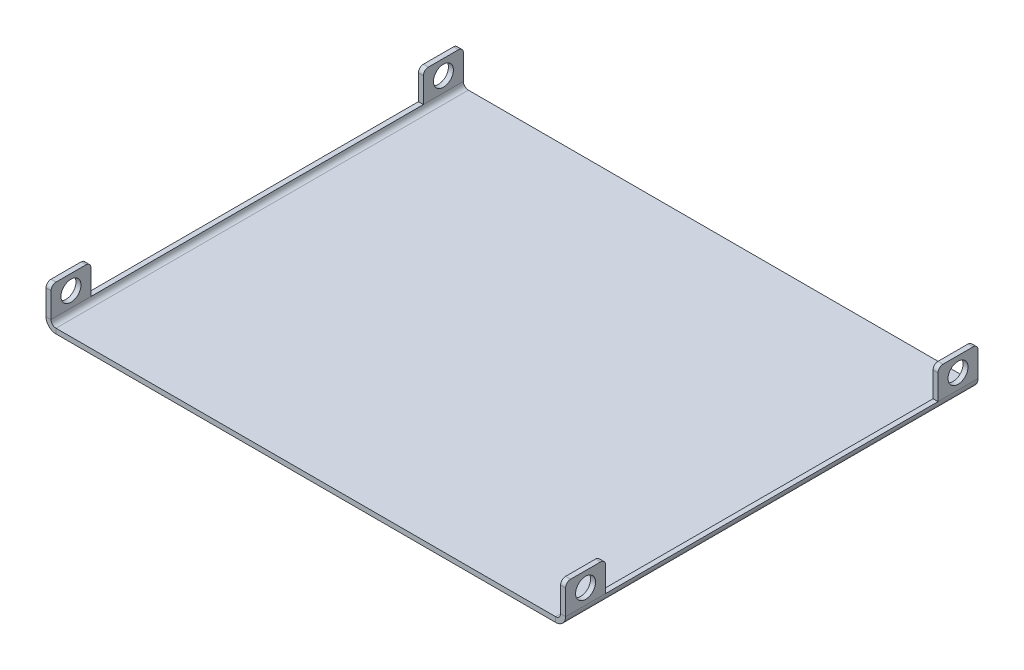
SolidWorks part; units mm, degrees
note: The reader was unsure of these and kept them because the rebuilt part matched: flange length of "Edge-Flange1".
material "6061-T6 (SS)"
ref_plane "Front Plane" through (0, 0, 0) normal (0, 0, 1) x (1, 0, 0)
ref_plane "Top Plane" through (0, 0, 0) normal (0, 1, 0) x (1, 0, 0)
ref_plane "Right Plane" through (0, 0, 0) normal (1, 0, 0) x (0, 0, -1)
sketch "Sketch1" plane through (0, 0, 0) normal (0, 1, 0) x (1, 0, 0)
  line L2 (0, 0) -> (0, 82.6)
  line L4 (104.072, 0) -> (104.072, 82.6)
  line L31 (0, 82.6) -> (104.072, 82.6)
  line L32 (0, 0) -> (104.072, 0)
  dimension "D1" = 82.6
  dimension "D2" = 104.072
  dimension "D3" = 90
base flange "Base-Flange2" sketch "Sketch1" thickness 1 reverse thickness direction no parameters "D1"=1
edge flange "Edge-Flange1" sketch "Sketch14" flange profiles "Sketch14", "Sketch15" flange angle 90 flange length 8 flange position material inside bend radius 1 thickness 1 relief rectangular parameters "D6"=10, "D8"=1
sketch "Sketch14" plane through (104.072, 0, 0) normal (1, 0, 0) x (0, 0, -1)
  line L0 (0, 0) -> (82.6, 0) construction
  line L1 (0, 0) -> (82.6, 0)
  line L2 (0, 0) -> (0, 7)
  line L3 (0, 7) -> (82.6, 7)
  line L4 (82.6, 7) -> (82.6, 0)
  dimension "D1" = 7
sketch "Sketch15" plane through (0, 0, 0) normal (-1, 0, 0) x (0, 0, 1)
  line L0 (-82.6, 0) -> (0, 0) construction
  line L1 (-82.6, 0) -> (0, 0)
  line L2 (-82.6, 0) -> (-82.6, 7)
  line L3 (-82.6, 7) -> (0, 7)
  line L4 (0, 7) -> (0, 0)
  dimension "D1" = 7
bend "EdgeBend1" bend radius 1 bend angle 90 parameters "D5"=1
bend "EdgeBend2" bend radius 1 bend angle 90 parameters "D5"=2
sketch "Sketch16" plane through (104.072, 0, 0) normal (1, 0, 0) x (0, 0, -1)
  line L0 (82.6, 1) -> (0, 1) construction
  line L1 (8, 8) -> (74.6, 8)
  line L2 (8, 8) -> (8, 1)
  line L3 (8, 1) -> (74.6, 1)
  line L4 (74.6, 8) -> (74.6, 1)
  line L5 (0, 7) -> (0, 1) construction
  line L6 (82.6, 1) -> (82.6, 7) construction
  line L7 (82.6, 7) -> (0, 7) construction
  dimension "D1" = 8
  dimension "D2" = 8
  dimension "D3" = 1
extrude "Cut-Extrude1" cut sketch "Sketch16" against normal through all normal cut yes
fillet "Fillet1" radius 1 8 edges at (0.5, 7, -8) (0.5, 7, 0) (0.5, 7, -74.6) (0.5, 7, -82.6) (103.572, 7, -74.6) (103.572, 7, -82.6) (103.572, 7, 0) (103.572, 7, -8)
sketch "Sketch17" plane through (104.072, 0, 0) normal (1, 0, 0) x (0, 0, -1)
  line L0 (8, 1) -> (0, 1) construction
  line L1 (0, 6) -> (0, 1) construction
  line L2 (82.6, 1) -> (74.6, 1) construction
  line L3 (82.6, 1) -> (82.6, 6) construction
  circle A0 centre (4, 4) radius 2
  circle A1 centre (78.6, 4) radius 2
  dimension "D1" = 4
  dimension "D4" = 4
  dimension "D2" = 3
  dimension "D3" = 4
  dimension "D5" = 3
  dimension "D6" = 4
extrude "Cut-Extrude2" cut sketch "Sketch17" against normal through all normal cut yes
sketch "Bend-Lines3" [suppressed] plane through (0, 0, 0) normal (0, 1, 0) x (1, 0, 0)
sketch "Bounding-Box3" [suppressed] plane through (0, 0, 0) normal (0, 1, 0) x (1, 0, 0)
sheet metal parameters "Sheet-Metal2" thickness 1 parameters "D1"=1
flat pattern "Flat-Pattern2" [suppressed]
sketch "Bend-Lines4" plane through (0, 0, 0) normal (0, 1, 0) x (1, 0, 0)
sketch3d "Bounding-Box4" [suppressed]
  line L0 (-135.6338, 86.2583, 0) -> (0, 86.2583, 0) construction
  line L1 (-135.6338, 0, 0) -> (0, 0, 0) construction
  line L2 (-135.6338, 86.2583, 0) -> (-135.6338, 0, 0) construction
  line L3 (0, 86.2583, 0) -> (0, 0, 0) construction
sheet metal parameters "Sheet-Metal3" thickness 1 parameters "D1"=1
flat pattern "Flat-Pattern2"
sketch "Bend-Lines4" plane through (0, 0, 0) normal (0, 1, 0) x (1, 0, 0)
sketch3d "Bounding-Box4" [suppressed]
  line L0 (-135.6338, 86.2583, 0) -> (0, 86.2583, 0) construction
  line L1 (-135.6338, 0, 0) -> (0, 0, 0) construction
  line L2 (-135.6338, 86.2583, 0) -> (-135.6338, 0, 0) construction
  line L3 (0, 86.2583, 0) -> (0, 0, 0) construction
bend of the flat pattern "Flatten-<EdgeBend1>1"
bend of the flat pattern "Flatten-<EdgeBend2>1"
sheet metal parameters "Sheet-Metal4" thickness 1 parameters "D1"=1
flat pattern "Flat-Pattern2"
sketch "Bend-Lines4" plane through (0, 0, 0) normal (0, 1, 0) x (1, 0, 0)
sketch3d "Bounding-Box4" [suppressed]
  line L0 (-135.6338, 86.2583, 0) -> (0, 86.2583, 0) construction
  line L1 (-135.6338, 0, 0) -> (0, 0, 0) construction
  line L2 (-135.6338, 86.2583, 0) -> (-135.6338, 0, 0) construction
  line L3 (0, 86.2583, 0) -> (0, 0, 0) construction
bend of the flat pattern "Flatten-<EdgeBend1>1"
bend of the flat pattern "Flatten-<EdgeBend2>1"
sheet metal parameters "Sheet-Metal5" thickness 1 parameters "D1"=1
flat pattern "Flat-Pattern2"
sketch "Bend-Lines4" plane through (0, 0, 0) normal (0, 1, 0) x (1, 0, 0)
sketch3d "Bounding-Box4" [suppressed]
  line L0 (-135.6338, 86.2583, 0) -> (0, 86.2583, 0) construction
  line L1 (-135.6338, 0, 0) -> (0, 0, 0) construction
  line L2 (-135.6338, 86.2583, 0) -> (-135.6338, 0, 0) construction
  line L3 (0, 86.2583, 0) -> (0, 0, 0) construction
bend of the flat pattern "Flatten-<EdgeBend1>1"
bend of the flat pattern "Flatten-<EdgeBend2>1"
